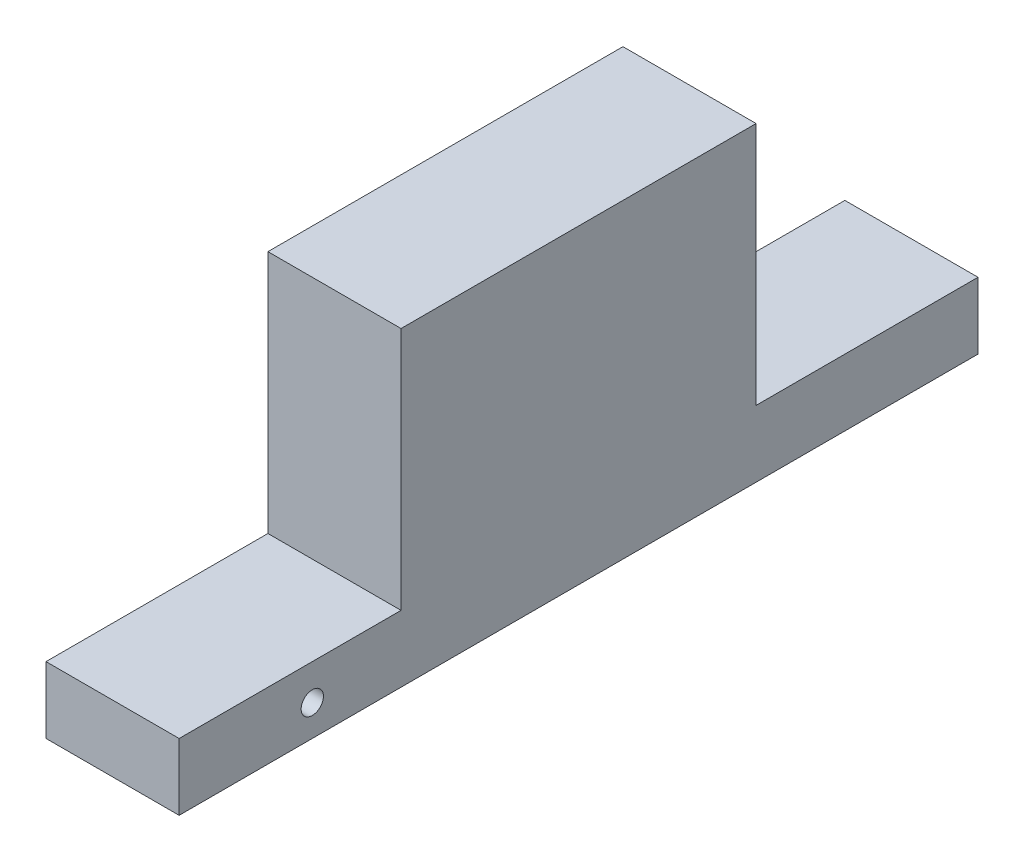
SolidWorks part; units mm, degrees
ref_plane "xy_plane" through (0, 0, 0) normal (0, 0, 1) x (1, 0, 0)
ref_plane "zx_plane" through (0, 0, 0) normal (0, 1, 0) x (1, 0, 0)
ref_plane "yz_plane" through (0, 0, 0) normal (1, 0, 0) x (0, 0, -1)
ref_axis "x_axis" through (-80.9, 0, 0) along (1, 0, 0)
ref_axis "y_axis" through (0, -50, 0) along (0, 1, 0)
ref_axis "z_axis" through (0, 0, -80.9) along (0, 0, 1)
ref_plane "xMid_plane" through (0, 0, 0) normal (1, 0, 0) x (0, 0, -1)
ref_plane "xMin_plane" through (-15, 0, 0) normal (1, 0, 0) x (0, 0, -1)
ref_plane "xMax_plane" through (15, 0, 0) normal (1, 0, 0) x (0, 0, -1)
ref_plane "yMid_plane" through (0, 0, 0) normal (0, 1, 0) x (1, 0, 0)
ref_plane "yMin_plane" through (0, -35, 0) normal (0, 1, 0) x (1, 0, 0)
ref_plane "yMax_plane" through (0, 35, 0) normal (0, 1, 0) x (1, 0, 0)
ref_plane "zMid_plane" through (0, 0, 0) normal (0, 0, 1) x (1, 0, 0)
ref_plane "zMin_plane" through (0, 0, -90) normal (0, 0, 1) x (1, 0, 0)
ref_plane "zMax_plane" through (0, 0, 90) normal (0, 0, 1) x (1, 0, 0)
sketch "projectionYz_sketch" plane through (0, 0, 0) normal (1, 0, 0) x (0, 0, -1)
  line L0 (90, -35) -> (90, -20)
  line L1 (90, -20) -> (40, -20)
  line L2 (40, -20) -> (40, 35)
  line L3 (40, 35) -> (-40, 35)
  line L4 (-40, 35) -> (-40, -20)
  line L5 (-40, -20) -> (-90, -20)
  line L6 (-90, -20) -> (-90, -35)
  line L7 (90, -35) -> (-90, -35)
  line L8 (90, 55) -> (90, -55) construction
  line L9 (55, -35) -> (-55, -35) construction
  line L10 (-90, 55) -> (-90, -55) construction
  line L11 (40, 90) -> (40, -20) construction
  line L12 (-40, 90) -> (-40, -20) construction
  line L13 (55, 35) -> (-55, 35) construction
  dimension "D1" = 15
extrude "mainBody_extrude" add sketch "projectionYz_sketch" along normal up to surface (15 mm away) from surface up to plane "xMax_plane" starting at plane "xMin_plane"
sketch "pivotShaftHole_sketch" plane through (0, 0, 0) normal (1, 0, 0) x (0, 0, -1)
  circle A0 centre (-60, -28) radius 2.51
  point P2 (0, 0)
  dimension "D1" = 5.02
extrude "pivotShaftHole_cut" cut sketch "pivotShaftHole_sketch" against normal through all both and the other way through all from surface starting at plane "xMid_plane"
equation "\"D1@xMin_plane\"= \"externalParameters.this.extentX\" / 2"
equation "\"D1@xMax_plane\" = \"externalParameters.this.extentX\" / 2"
equation "\"D1@yMin_plane\" = \"externalParameters.this.extentY\" / 2"
equation "\"D1@yMax_plane\" = \"externalParameters.this.extentY\" / 2"
equation "\"D1@zMin_plane\" = \"externalParameters.this.extentZ\" / 2"
equation "\"D1@zMax_plane\" = \"externalParameters.this.extentZ\" / 2"
equation "\"D1@projectionYz_sketch\"=\"externalParameters.this.foot.extentY\""
equation "\"D1@pivotShaftHole_sketch\"=\"externalParameters.pivotShaft.holeDiameter\""
